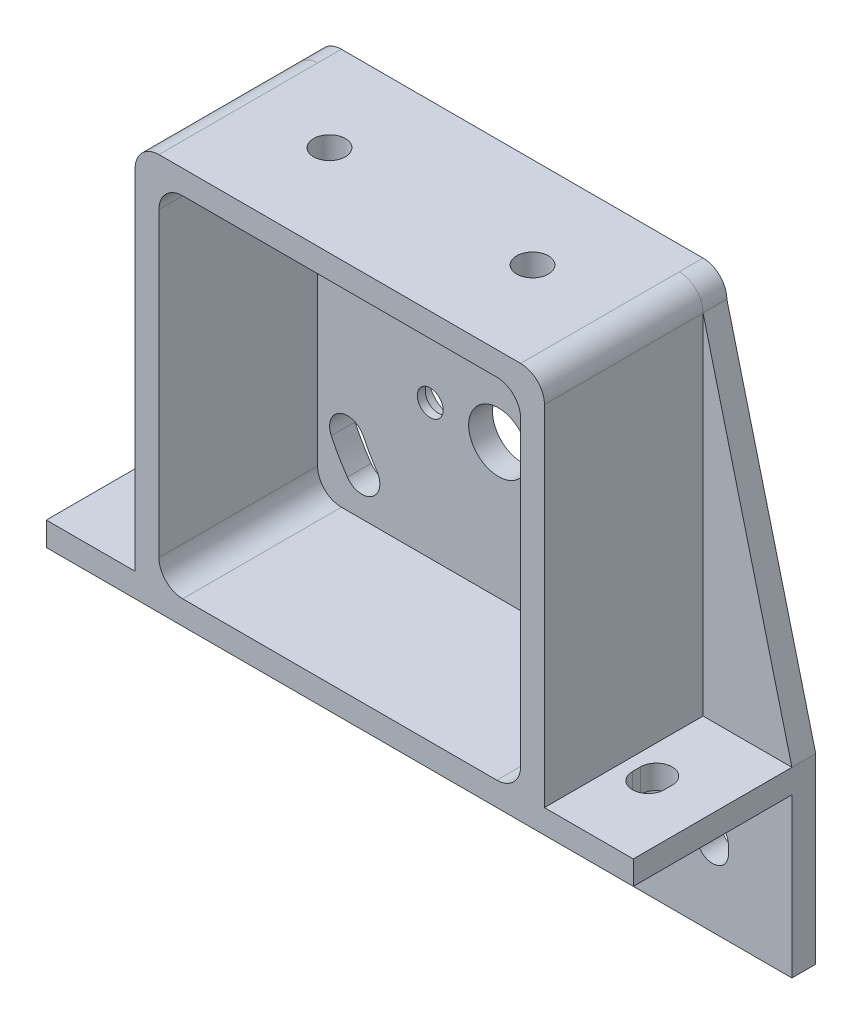
SolidWorks part; units mm, degrees
ref_plane "Front Plane" through (0, 0, 0) normal (0, 0, 1) x (1, 0, 0)
ref_plane "Top Plane" through (0, 0, 0) normal (0, 1, 0) x (1, 0, 0)
ref_plane "Right Plane" through (0, 0, 0) normal (1, 0, 0) x (0, 0, -1)
sketch "Sketch1" plane through (0, 0, 0) normal (0, 0, 1) x (1, 0, 0)
  line L0 (8, 10.5) -> (8, 9.5)
  line L1 (0, 0) -> (74, 0)
  line L2 (0, 0) -> (0, 70)
  line L3 (0, 70) -> (74, 70)
  line L4 (74, 0) -> (74, 70)
  line L5 (12, 10.5) -> (12, 9.5)
  line L6 (37, 0) -> (37, 58.75) construction
  line L7 (66, 10.5) -> (66, 9.5)
  line L8 (62, 10.5) -> (62, 9.5)
  line L9 (37, 40) -> (37, 16.9053) construction
  line L11 (37, 63.25) -> (37, 70) construction
  circle A0 centre (37, 40) radius 3.75
  circle A1 centre (28.4, 40) radius 1.625
  circle A2 centre (45.6, 40) radius 1.625
  arc A20 (8, 9.5) -> (12, 9.5) centre (10, 9.5) ccw
  arc A22 (66, 9.5) -> (62, 9.5) centre (64, 9.5) cw
  arc A23 (12, 10.5) -> (8, 10.5) centre (10, 10.5) ccw
  arc A24 (62, 10.5) -> (66, 10.5) centre (64, 10.5) cw
  arc A27 (34.9736, 63.1615) -> (35.3658, 58.6787) centre (35.1697, 60.9201) ccw
  arc A28 (38.6342, 58.6787) -> (35.3658, 58.6787) centre (37, 40) ccw
  arc A29 (39.0264, 63.1615) -> (34.9736, 63.1615) centre (37, 40) ccw
  arc A31 (15.9283, 30.1741) -> (20.0067, 32.0759) centre (17.9675, 31.125) cw
  arc A32 (38.6342, 58.6787) -> (39.0264, 63.1615) centre (38.8303, 60.9201) ccw
  arc A33 (21.6409, 29.2454) -> (20.0067, 32.0759) centre (37, 40) cw
  arc A34 (17.9547, 26.6643) -> (15.9283, 30.1741) centre (37, 40) cw
  arc A35 (21.6409, 29.2454) -> (17.9547, 26.6643) centre (19.7978, 27.9549) cw
  arc A36 (58.0717, 30.1741) -> (53.9933, 32.0759) centre (56.0325, 31.125) ccw
  arc A37 (56.0453, 26.6643) -> (58.0717, 30.1741) centre (37, 40) ccw
  arc A38 (52.3591, 29.2454) -> (56.0453, 26.6643) centre (54.2022, 27.9549) ccw
  arc A39 (52.3591, 29.2454) -> (53.9933, 32.0759) centre (37, 40) ccw
  dimension "D4" = 7.5
  dimension "D6" = 3.25
  dimension "D9" = 3.25
  dimension "D12" = 2.25
  dimension "D13" = 21
  dimension "D14" = 21
  dimension "D15" = 4.5
  dimension "D21" = 9.5
  dimension "D23" = 4
  dimension "D24" = 10
  dimension "D1" = 74
  dimension "D2" = 70
  dimension "D3" = 40
  dimension "D5" = 37
  dimension "D7" = 8.6
  dimension "D8" = 40
  dimension "D10" = 8.6
  dimension "D11" = 40
  dimension "D22" = 1
  dimension "D25" = 10
extrude "Boss-Extrude1" add sketch "Sketch1" along normal blind 3
sketch "Sketch2" plane through (0, 0, 3) normal (0, 0, 1) x (1, 0, 0)
  line L0 (0, 70) -> (0, 0) construction
  line L2 (0, 23) -> (74, 23)
  line L4 (0, 23) -> (0, 20)
  line L5 (0, 20) -> (74, 20)
  line L6 (74, 23) -> (74, 20)
  line L7 (74, 0) -> (74, 70) construction
  line L8 (0, 0) -> (74, 0) construction
  point P9 (37, 20)
  dimension "D1" = 20
  dimension "D2" = 3
ref_plane "Plane1" through (0, 0, 23) normal (0, 0, 1) x (1, 0, 0)
sketch "Sketch3" plane through (0, 0, 23) normal (0, 0, 1) x (1, 0, 0)
  line L0 (0, 20) -> (74, 20) construction
  line L1 (0, 23) -> (74, 23)
  line L2 (0, 23) -> (0, 20)
  line L3 (0, 20) -> (74, 20)
  line L4 (74, 23) -> (74, 20)
  point P4 (37, 20)
  point P7 (37, 20)
  dimension "D1" = 74
  dimension "D2" = 3
  dimension "D3" = 0
  dimension "D4" = 0
loft "Loft1" add profiles "Sketch2", "Sketch3" connector at (0, 20, 3) connector at (0, 20, 23)
sketch "Sketch4" plane through (0, 0, 3) normal (0, 0, 1) x (1, 0, 0)
  line L1 (74, 70) -> (0, 70) construction
  line L3 (0, 23) -> (74, 23) construction
  line L5 (74, 23) -> (0, 23) construction
  line L7 (14.2, 23) -> (14.2, 67)
  line L8 (14.2, 67) -> (59.8, 67)
  line L9 (59.8, 67) -> (59.8, 23)
  line L12 (11.2, 23) -> (11.2, 70)
  line L15 (62.8, 23) -> (62.8, 70)
  line L17 (11.2, 70) -> (62.8, 70)
  line L18 (0, 70) -> (0, 23) construction
  line L20 (59.8, 23) -> (62.8, 23)
  line L21 (11.2, 23) -> (14.2, 23)
  point P0 (11.2, 46.5)
  point P5 (0, 46.5)
  point P7 (62.8, 46.5)
  point P8 (14.2, 45)
  point P11 (59.8, 45)
  dimension "D1" = 11.2
  dimension "D2" = 3
  dimension "D3" = 11.2
  dimension "D4" = 3
  dimension "D6" = 44
extrude "Boss-Extrude2" add sketch "Sketch4" along normal blind 20
ref_plane "Plane2" through (0, 23, 23) normal (-1, 0, 0) x (0, 0, 1)
sketch "Sketch8" plane through (0, 23, 0) normal (0, 1, 0) x (1, 0, 0)
  line L4 (37, -3) -> (37, -23) construction
  line L5 (59.8, -3) -> (14.2, -3) construction
  line L6 (59.8, -23) -> (14.2, -23) construction
  line L9 (5.6, -12.5) -> (5.6, -13.5)
  line L10 (9.6, -12.5) -> (9.6, -13.5)
  line L11 (68.4, -12.5) -> (68.4, -13.5)
  line L12 (64.4, -12.5) -> (64.4, -13.5)
  arc A3 (5.6, -13.5) -> (9.6, -13.5) centre (7.6, -13.5) ccw
  arc A4 (64.4, -12.5) -> (68.4, -12.5) centre (66.4, -12.5) cw
  arc A5 (9.6, -12.5) -> (5.6, -12.5) centre (7.6, -12.5) ccw
  arc A6 (68.4, -13.5) -> (64.4, -13.5) centre (66.4, -13.5) cw
  dimension "D5" = 4
extrude "Cut-Extrude2" cut sketch "Sketch8" against normal blind 3
fillet "Fillet1" radius 3 1 edges at (11.2, 70, 13) type face fillet first side face at (37, 70, 7.25) second side face at (11.2, 52.375, 15.5)
fillet "Fillet2" radius 3 1 edges at (62.8, 70, 13) type face fillet first side face at (37.75, 70, 7.25) second side face at (62.8, 40.625, 15.5)
fillet "Fillet4" radius 3 1 edges at (59.8, 67, 13) type face fillet first side face at (37, 67, 13) second side face at (59.8, 50.5, 15.5)
fillet "Fillet5" radius 3 1 edges at (14.2, 67, 13) type face fillet first side face at (35.5, 67, 13) second side face at (14.2, 39.5, 15.5)
sketch "Sketch10" plane through (0, 0, 3) normal (0, 0, 1) x (1, 0, 0)
  line L0 (0, 23) -> (11.2, 67)
  line L1 (11.2, 67) -> (11.2, 70)
  line L2 (14.2, 70) -> (0, 70) construction
  line L3 (11.2, 70) -> (0, 70)
  line L4 (0, 70) -> (0, 23)
  line L5 (74, 23) -> (62.8, 67)
  line L6 (62.8, 67) -> (62.8, 70)
  line L7 (74, 70) -> (59.8, 70) construction
  line L8 (62.8, 70) -> (74, 70)
  line L9 (74, 70) -> (74, 23)
extrude "Cut-Extrude4" cut sketch "Sketch10" against normal blind 3
fillet "Fillet6" radius 3 1 edges at (62.8, 70, 1.5) type face fillet first side face at (62.8, 68.5, 1.5) second side face at (37, 70, 7.25)
fillet "Fillet7" radius 3 1 edges at (11.2, 70, 1.5) type face fillet first side face at (32.8857, 70, 7.8571) second side face at (11.2, 68.5, 1.5)
fillet "Fillet8" radius 3 1 edges type face fillet first side face at (14.2, 38.375, 15.5) second side face at (48.4, 23, 18)
fillet "Fillet9" radius 3 1 edges type face fillet first side face at (59.8, 48.625, 15.5) second side face at (49.15, 23, 13)
sketch "Sketch11" plane through (0, 70, 0) normal (0, 1, 0) x (1, 0, 0)
  line L0 (59.8, 0) -> (14.2, 0) construction
  line L1 (14.2, -3) -> (14.2, -23) construction
  line L4 (37, 0) -> (37, -23) construction
  line L5 (59.8, -23) -> (14.2, -23) construction
  circle A0 centre (24.2, -11.5) radius 2
  circle A1 centre (49.8, -11.5) radius 2
  dimension "D3" = 4
  dimension "D1" = 11.5
  dimension "D2" = 10
extrude "Cut-Extrude5" cut sketch "Sketch11" against normal blind 3
sketch "Sketch12" plane through (0, 0, 0) normal (0, 0, -1) x (-1, 0, 0)
  circle A0 centre (-45.6, 40) radius 3.25
  circle A1 centre (-28.4, 40) radius 3.25
  dimension "D1" = 6.5
  dimension "D2" = 6.5
extrude "Cut-Extrude6" cut sketch "Sketch12" against normal blind 2
